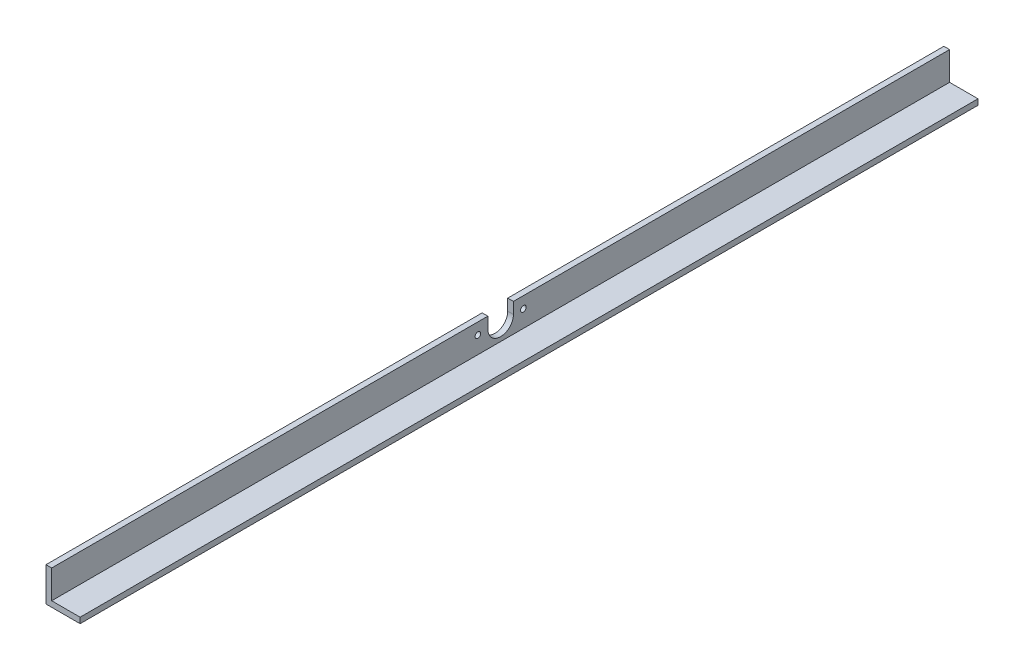
SolidWorks part; units mm, degrees
ref_plane "Front Plane" through (0, 0, 0) normal (0, 0, 1) x (1, 0, 0)
ref_plane "Top Plane" through (0, 0, 0) normal (0, 1, 0) x (1, 0, 0)
ref_plane "Right Plane" through (0, 0, 0) normal (1, 0, 0) x (0, 0, -1)
sketch "Sketch1" plane through (0, 0, 0) normal (0, 0, 1) x (1, 0, 0)
  line L0 (0, 0) -> (0, 38.1)
  line L1 (0, 38.1) -> (6.35, 38.1)
  line L2 (6.35, 38.1) -> (6.35, 6.35)
  line L3 (6.35, 6.35) -> (0, 0) construction
  line L4 (38.1, 6.35) -> (6.35, 6.35)
  line L5 (38.1, 0) -> (38.1, 6.35)
  line L6 (0, 0) -> (38.1, 0)
  dimension "D1" = 45
  dimension "D2" = 38.1
  dimension "D3" = 6.35
extrude "Boss-Extrude1" add sketch "Sketch1" along normal blind 1003.3
sketch "Sketch2" plane through (6.35, 0, 0) normal (1, 0, 0) x (0, 0, -1)
  line L0 (-501.65, 0) -> (-501.65, 25.4) construction
  line L3 (-1003.3, 0) -> (0, 0) construction
  line L4 (-515.9375, 25.4) -> (-515.9375, 38.1)
  line L5 (-1003.3, 38.1) -> (0, 38.1) construction
  line L6 (-487.3625, 25.4) -> (-487.3625, 38.1)
  line L7 (-487.3625, 38.1) -> (-487.3625, 50.2994)
  line L8 (-487.3625, 50.2994) -> (-515.9375, 50.2994)
  line L9 (-515.9375, 50.2994) -> (-515.9375, 38.1)
  line L10 (-501.65, 25.4) -> (-527.05, 25.4) construction
  line L11 (-527.05, 25.4) -> (-527.05, 38.1) construction
  circle A0 centre (-501.65, 25.4) radius 14.2875
  circle A1 centre (-527.05, 25.4) radius 3.175
  circle A2 centre (-476.25, 25.4) radius 3.175
  line M4 (0, 38.1) -> (-1003.3, 38.1)
  dimension "D1" = 28.575
  dimension "D5" = 6.35
  dimension "D2" = 25.4
  dimension "D3" = 25.4
  dimension "D4" = 12.7
extrude "Cut-Extrude1" cut sketch "Sketch2" against normal up to next contours A0 M4 | A0 L4 M4 | A0 L6 M4 | A1 | A2 region at (6.35, 25.102, 501.65) region at (6.35, 35.1217, 513.7847) region at (6.35, 35.1217, 489.5153) region at (6.35, 25.4, 527.05)
